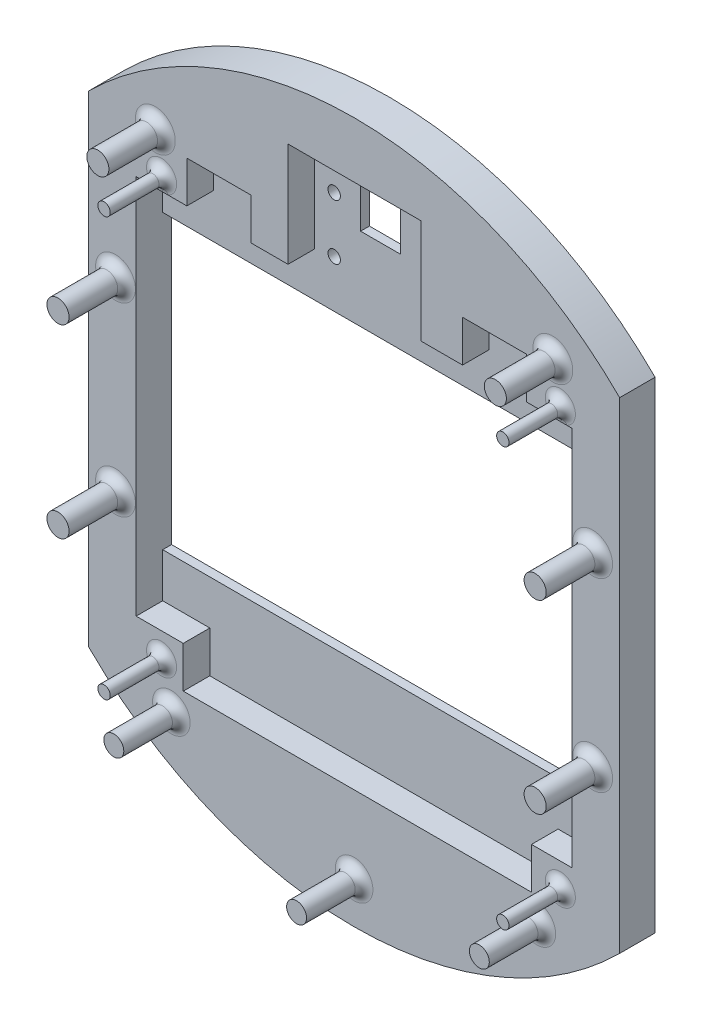
SolidWorks part; units mm, degrees
material "ABS"
ref_plane "Plano frontal" through (0, 0, 0) normal (0, 0, 1) x (1, 0, 0)
ref_plane "Plano superior" through (0, 0, 0) normal (0, 1, 0) x (1, 0, 0)
ref_plane "Plano direito" through (0, 0, 0) normal (1, 0, 0) x (0, 0, -1)
sketch "Esboço1" plane through (0, 0, 0) normal (0, 0, 1) x (1, 0, 0)
  line L0 (0, 0) -> (0, -108.75)
  line L1 (120, -108.75) -> (120, 0)
  line L2 (60, -11.4098) -> (60, -97.3402) construction
  line L3 (120, -54.375) -> (-37.4329, -54.375) construction
  line L4 (10.75, -87.375) -> (109.25, -87.375)
  line L5 (10.75, -87.375) -> (10.75, -21.375)
  line L6 (10.75, -21.375) -> (109.25, -21.375)
  line L7 (109.25, -87.375) -> (109.25, -21.375)
  line L8 (10.75, -87.375) -> (109.25, -21.375) construction
  line L9 (10.75, -21.375) -> (109.25, -87.375) construction
  arc A4 (0, 0) -> (120, 0) centre (60, -60.208) cw
  arc A5 (0, -108.75) -> (120, -108.75) centre (60, -48.542) ccw
  point P9 (60, -54.375)
  point P17 (60, 24.792)
  dimension "D1" = 108.75
  dimension "D5" = 85
  dimension "D2" = 66
  dimension "D3" = 98.5
extrude "Ressalto-extrusão1" add sketch "Esboço1" along normal blind 8
sketch "Esboço2" plane through (0, 0, 8) normal (0, 0, 1) x (1, 0, 0)
  line L0 (10.75, -54.375) -> (109.25, -54.375) construction
  line L1 (10.75, -21.375) -> (10.75, -87.375) construction
  line L2 (109.25, -87.375) -> (109.25, -21.375) construction
  line L3 (109.25, -21.375) -> (10.75, -21.375) construction
  line L4 (10.75, -97.375) -> (109.25, -97.375)
  line L5 (10.75, -97.375) -> (10.75, -11.375)
  line L6 (10.75, -11.375) -> (109.25, -11.375)
  line L7 (109.25, -97.375) -> (109.25, -11.375)
  line L8 (10.75, -97.375) -> (109.25, -11.375) construction
  line L9 (10.75, -11.375) -> (109.25, -97.375) construction
  point P6 (60, -54.375)
  dimension "D1" = 10
extrude "Corte-extrusão1" cut sketch "Esboço2" against normal blind 6
sketch "Esboço3" plane through (0, 0, 8) normal (0, 0, 1) x (1, 0, 0)
  line L0 (-24.8022, -47.1436) -> (153.0643, -47.1436) construction
  line L1 (113.9062, -94.6477) -> (113.9062, -101.6218) construction
  line L2 (6.0938, 0) -> (113.9062, 0) construction
  line L3 (60, 24.792) -> (60, -133.542) construction
  line L5 (0, 0) -> (0, -108.75) construction
  line L6 (0, -12.5) -> (6.0938, -12.5) construction
  line L7 (6.0938, -12.5) -> (6.0938, -102.188) construction
  line L8 (35.13, -11.375) -> (35.13, -106.875) construction
  line L9 (109.25, -11.375) -> (10.75, -11.375) construction
  line L10 (60, -133.542) -> (60, -106.875)
  arc A0 (6.0938, -102.188) -> (113.9062, -102.188) centre (60, -47.1436) ccw
  circle A1 centre (18.7084, -112.188) radius 2.25
  circle A2 centre (60, -124.1876) radius 2.25
  circle A3 centre (101.2916, -112.188) radius 2.25
  circle A4 centre (104.9062, 0) radius 2.5
  circle A6 centre (15.0938, 0) radius 2.5
  arc A7 (120, 0) -> (0, 0) centre (60, -60.208) ccw construction
  arc A8 (0, -108.75) -> (120, -108.75) centre (60, -48.542) ccw construction
  circle A9 centre (6.0938, -75.315) radius 2.5
  circle A10 centre (6.0938, -33.44) radius 2.5
  circle A11 centre (113.9062, -75.315) radius 2.5
  circle A12 centre (113.9062, -33.44) radius 2.5
  point P39 (60, -11.375)
  dimension "D1" = 4.5
  dimension "D2" = 5
  dimension "D7" = 77.044
  dimension "D3" = 41.875
  dimension "D4" = 20.94
  dimension "D5" = 10
  dimension "D6" = 89.688
  dimension "D8" = 41.2916
  dimension "D9" = 26.667
  dimension "D10" = 36.167
  dimension "D11" = 9.3545
  dimension "D12" = 107.8125
  dimension "D13" = 9
  dimension "D14" = 9
extrude "Ressalto-extrusão2" add sketch "Esboço3" along normal blind 13 contours A9 | A1 | A2 | A3 | A11 | A12 | A4 | A6 | A10
fillet "Filete1" radius 2 9 edges at (12.5938, 0, 8) (3.5937, -33.44, 8) (3.5937, -75.315, 8) (16.4584, -112.188, 8) (57.75, -124.1876, 8) (99.0416, -112.188, 8) (111.4062, -75.315, 8) (111.4063, -33.44, 8) (102.4062, 0, 8)
sketch "Esboço5" plane through (0, 0, 8) normal (0, 0, 1) x (1, 0, 0)
  line L0 (47.0593, -11.375) -> (47.0593, 1.21)
  line L1 (109.25, -11.375) -> (10.75, -11.375) construction
  line L2 (47.0593, 1.21) -> (73.076, 1.21)
  line L3 (73.076, 1.21) -> (73.076, -25.3836)
  line L4 (73.076, -25.3836) -> (47.0593, -25.3836)
  line L5 (47.0593, -25.3836) -> (47.0593, -11.375)
extrude "Corte-extrusão3" cut sketch "Esboço5" against normal blind 5
sketch "Esboço6" plane through (0, 0, 8) normal (0, 0, 1) x (1, 0, 0)
  line L0 (60, 24.792) -> (60, -141.3459) construction
  line L1 (0, -54.375) -> (135.5539, -54.375) construction
  line L2 (0, 0) -> (0, -108.75) construction
  circle A0 centre (16.5, -8.315) radius 1.4
  arc A1 (120, 0) -> (0, 0) centre (60, -60.208) ccw construction
  circle A5 centre (106.6, -102.835) radius 1.4
  circle A6 centre (16.5, -102.835) radius 1.4
  circle A7 centre (106.6, -8.315) radius 1.4
  dimension "D1" = 2.8
extrude "Ressalto-extrusão3" add sketch "Esboço6" along normal up to surface (13 mm away) up to face at (111.4062, -75.315, 21)
fillet "Filete2" radius 2 4 edges at (105.2, -8.315, 8) (15.1, -102.835, 8) (105.2, -102.835, 8) (15.1, -8.315, 8)
sketch "Esboço8" plane through (0, 0, 8) normal (0, 0, 1) x (1, 0, 0)
  line L0 (45.0677, 1.21) -> (45.0677, 12.1682)
  line L1 (45.0677, 12.1682) -> (75.0677, 12.1682)
  line L2 (75.0677, 12.1682) -> (75.0677, -15.935)
  line L3 (75.0677, -15.935) -> (45.0677, -15.935)
  line L4 (45.0677, -15.935) -> (45.0677, 1.21)
  line L5 (73.076, 1.21) -> (47.0593, 1.21) construction
  point P8 (60.0677, -15.935)
  point P11 (60.0677, 1.21)
  dimension "D1" = 30
extrude "Corte-extrusão5" cut sketch "Esboço8" against normal up to surface (6 mm away) up to face at (60, -16.375, 2)
sketch "Esboço9" plane through (0, 0, 2) normal (0, 0, 1) x (1, 0, 0)
  line L1 (55.4685, 6.3063) -> (64.4685, 6.3063)
  line L2 (55.4685, 6.3063) -> (55.4685, -2.6937)
  line L3 (55.4685, -2.6937) -> (64.4685, -2.6937)
  line L4 (64.4685, 6.3063) -> (64.4685, -2.6937)
  line L5 (55.4685, 6.3063) -> (64.4685, -2.6937) construction
  line L6 (55.4685, -2.6937) -> (64.4685, 6.3063) construction
  circle A0 centre (49.5, -10.635) radius 1.4
  circle A1 centre (49.5, 1.865) radius 1.4
  circle A2 centre (70.5, 1.865) radius 1.4
  circle A3 centre (70.5, -10.635) radius 1.4
  point P12 (59.9685, 1.8063)
  dimension "D3" = 2.8
  dimension "D1" = 9
  dimension "D2" = 9
extrude "Corte-extrusão6" cut sketch "Esboço9" against normal through all
sketch "Esboço10" plane through (0, 0, 8) normal (0, 0, 1) x (1, 0, 0)
  line L0 (21.3948, -97.375) -> (21.3948, -106.7323)
  line L1 (10.75, -97.375) -> (109.25, -97.375) construction
  line L2 (21.3948, -106.7323) -> (100.0821, -106.7323)
  line L3 (100.0821, -106.7323) -> (100.0821, -95.2323)
  line L4 (100.0821, -95.2323) -> (21.3948, -95.2323)
  line L5 (21.3948, -95.2323) -> (21.3948, -97.375)
  line L6 (60, 24.792) -> (60, -137.3046) construction
  line L7 (0, -54.375) -> (133.7853, -54.375) construction
  line L8 (0, 0) -> (0, -108.75) construction
  line L14 (98.9669, -12.0402) -> (98.9669, -2.0177)
  line L15 (98.9669, -2.0177) -> (84.4999, -2.0177)
  line L16 (84.4999, -2.0177) -> (84.4999, -13.5177)
  line L17 (84.4999, -13.5177) -> (98.9669, -13.5177)
  line L18 (98.9669, -13.5177) -> (98.9669, -12.0402)
  line L19 (22.2093, -13.5177) -> (22.2093, -11.875)
  line L20 (36.7519, -13.5177) -> (22.2093, -13.5177)
  line L21 (36.7519, -2.0177) -> (36.7519, -13.5177)
  line L22 (22.2093, -2.0177) -> (36.7519, -2.0177)
  line L23 (22.2093, -11.875) -> (22.2093, -2.0177)
  arc A0 (120, 0) -> (0, 0) centre (60, -60.208) ccw construction
  dimension "D2" = 11.5
extrude "Corte-extrusão7" cut sketch "Esboço10" against normal up to surface (6 mm away) up to face at (50.9, 1.865, 2)
